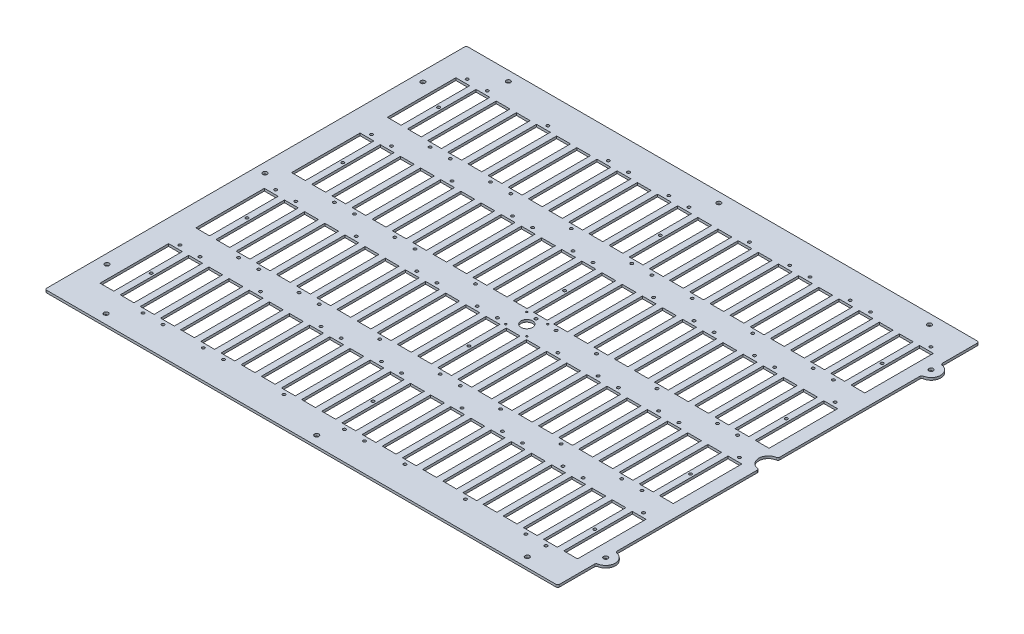
SolidWorks part; units mm, degrees
ref_plane "Front Plane" through (0, 0, 0) normal (0, 0, 1) x (1, 0, 0)
ref_plane "Top Plane" through (0, 0, 0) normal (0, 1, 0) x (1, 0, 0)
ref_plane "Right Plane" through (0, 0, 0) normal (1, 0, 0) x (0, 0, -1)
sketch "Sketch1" plane through (0, 0, 0) normal (0, 1, 0) x (1, 0, 0)
  line L0 (340.2584, 228.6) -> (340.2584, 279.5524)
  line L1 (-340.2584, -279.5524) -> (340.2584, -279.5524)
  line L2 (-340.2584, -279.5524) -> (-340.2584, 279.5524)
  line L3 (-340.2584, 279.5524) -> (340.2584, 279.5524)
  line L4 (340.2584, -279.5524) -> (340.2584, -228.6)
  line L5 (-340.2584, -279.5524) -> (340.2584, 279.5524) construction
  line L6 (-340.2584, 279.5524) -> (340.2584, -279.5524) construction
  line L7 (340.2584, 12.7) -> (340.2584, 203.2)
  line L8 (340.2584, -203.2) -> (340.2584, -12.7)
  arc A0 (340.2584, 203.2) -> (340.2584, 228.6) centre (340.2584, 215.9) ccw
  arc A1 (340.2584, -228.6) -> (340.2584, -203.2) centre (340.2584, -215.9) ccw
  arc A2 (340.2584, 12.7) -> (340.2584, -12.7) centre (340.2584, 0) ccw
  point P0 (0, 0)
  dimension "D3" = 25.4
  dimension "D4" = 63.6524
  dimension "D5" = 215.9
  dimension "D6" = 215.9
  dimension "D1" = 559.1048
  dimension "D2" = 680.5168
extrude "Boss-Extrude1" add sketch "Sketch1" along normal blind 3.175
sketch "Sketch17" plane through (0, 3.175, 0) normal (0, 1, 0) x (1, 0, 0)
  line L0 (340.2584, 279.5524) -> (-340.2584, 279.5524) construction
  line L1 (-314.8584, 254.1524) -> (327.5584, 254.1524) construction
  line L2 (-314.8584, 254.1524) -> (-314.8584, -254.1524) construction
  line L3 (-314.8584, -254.1524) -> (327.5584, -254.1524) construction
  line L4 (327.5584, 254.1524) -> (327.5584, -254.1524) construction
  line L5 (-340.2584, 279.5524) -> (-340.2584, -279.5524) construction
  line L6 (-340.2584, -279.5524) -> (340.2584, -279.5524) construction
  line L7 (340.2584, -203.2) -> (340.2584, -12.7) construction
  line L8 (-283.8406, 236.1184) -> (-265.5526, 236.1184)
  line L9 (-310.5912, 236.1184) -> (-292.3032, 236.1184)
  line L10 (-310.5912, 236.1184) -> (-310.5912, 145.1864)
  line L11 (-310.5912, 145.1864) -> (-292.3032, 145.1864)
  line L12 (-292.3032, 236.1184) -> (-292.3032, 145.1864)
  line L13 (-283.8406, 236.1184) -> (-283.8406, 145.1864)
  line L14 (-265.5526, 236.1184) -> (-265.5526, 145.1864)
  line L15 (-283.8406, 145.1864) -> (-265.5526, 145.1864)
  line L16 (-257.09, 236.1184) -> (-238.802, 236.1184)
  line L17 (-257.09, 236.1184) -> (-257.09, 145.1864)
  line L18 (-238.802, 236.1184) -> (-238.802, 145.1864)
  line L19 (-257.09, 145.1864) -> (-238.802, 145.1864)
  line L20 (-230.3393, 236.1184) -> (-212.0513, 236.1184)
  line L21 (-230.3393, 236.1184) -> (-230.3393, 145.1864)
  line L22 (-212.0513, 236.1184) -> (-212.0513, 145.1864)
  line L23 (-230.3393, 145.1864) -> (-212.0513, 145.1864)
  line L24 (-203.5887, 236.1184) -> (-185.3007, 236.1184)
  line L25 (-203.5887, 236.1184) -> (-203.5887, 145.1864)
  line L26 (-185.3007, 236.1184) -> (-185.3007, 145.1864)
  line L27 (-203.5887, 145.1864) -> (-185.3007, 145.1864)
  line L28 (-176.8381, 236.1184) -> (-158.5501, 236.1184)
  line L29 (-176.8381, 236.1184) -> (-176.8381, 145.1864)
  line L30 (-158.5501, 236.1184) -> (-158.5501, 145.1864)
  line L31 (-176.8381, 145.1864) -> (-158.5501, 145.1864)
  line L32 (-150.0875, 236.1184) -> (-131.7995, 236.1184)
  line L33 (-150.0875, 236.1184) -> (-150.0875, 145.1864)
  line L34 (-131.7995, 236.1184) -> (-131.7995, 145.1864)
  line L35 (-150.0875, 145.1864) -> (-131.7995, 145.1864)
  line L36 (-123.3369, 236.1184) -> (-105.0489, 236.1184)
  line L37 (-123.3369, 236.1184) -> (-123.3369, 145.1864)
  line L38 (-105.0489, 236.1184) -> (-105.0489, 145.1864)
  line L39 (-123.3369, 145.1864) -> (-105.0489, 145.1864)
  line L40 (-96.5863, 236.1184) -> (-78.2983, 236.1184)
  line L41 (-96.5863, 236.1184) -> (-96.5863, 145.1864)
  line L42 (-78.2983, 236.1184) -> (-78.2983, 145.1864)
  line L43 (-96.5863, 145.1864) -> (-78.2983, 145.1864)
  line L44 (-69.8356, 236.1184) -> (-51.5476, 236.1184)
  line L45 (-69.8356, 236.1184) -> (-69.8356, 145.1864)
  line L46 (-51.5476, 236.1184) -> (-51.5476, 145.1864)
  line L47 (-69.8356, 145.1864) -> (-51.5476, 145.1864)
  line L48 (-43.085, 236.1184) -> (-24.797, 236.1184)
  line L49 (-43.085, 236.1184) -> (-43.085, 145.1864)
  line L50 (-24.797, 236.1184) -> (-24.797, 145.1864)
  line L51 (-43.085, 145.1864) -> (-24.797, 145.1864)
  line L52 (-16.3344, 236.1184) -> (1.9536, 236.1184)
  line L53 (-16.3344, 236.1184) -> (-16.3344, 145.1864)
  line L54 (1.9536, 236.1184) -> (1.9536, 145.1864)
  line L55 (-16.3344, 145.1864) -> (1.9536, 145.1864)
  line L56 (10.4162, 236.1184) -> (28.7042, 236.1184)
  line L57 (10.4162, 236.1184) -> (10.4162, 145.1864)
  line L58 (28.7042, 236.1184) -> (28.7042, 145.1864)
  line L59 (10.4162, 145.1864) -> (28.7042, 145.1864)
  line L60 (37.1668, 236.1184) -> (55.4548, 236.1184)
  line L61 (37.1668, 236.1184) -> (37.1668, 145.1864)
  line L62 (55.4548, 236.1184) -> (55.4548, 145.1864)
  line L63 (37.1668, 145.1864) -> (55.4548, 145.1864)
  line L64 (63.9174, 236.1184) -> (82.2054, 236.1184)
  line L65 (63.9174, 236.1184) -> (63.9174, 145.1864)
  line L66 (82.2054, 236.1184) -> (82.2054, 145.1864)
  line L67 (63.9174, 145.1864) -> (82.2054, 145.1864)
  line L68 (90.6681, 236.1184) -> (108.9561, 236.1184)
  line L69 (90.6681, 236.1184) -> (90.6681, 145.1864)
  line L70 (108.9561, 236.1184) -> (108.9561, 145.1864)
  line L71 (90.6681, 145.1864) -> (108.9561, 145.1864)
  line L72 (117.4187, 236.1184) -> (135.7067, 236.1184)
  line L73 (117.4187, 236.1184) -> (117.4187, 145.1864)
  line L74 (135.7067, 236.1184) -> (135.7067, 145.1864)
  line L75 (117.4187, 145.1864) -> (135.7067, 145.1864)
  line L76 (144.1693, 236.1184) -> (162.4573, 236.1184)
  line L77 (144.1693, 236.1184) -> (144.1693, 145.1864)
  line L78 (162.4573, 236.1184) -> (162.4573, 145.1864)
  line L79 (144.1693, 145.1864) -> (162.4573, 145.1864)
  line L80 (170.9199, 236.1184) -> (189.2079, 236.1184)
  line L81 (170.9199, 236.1184) -> (170.9199, 145.1864)
  line L82 (189.2079, 236.1184) -> (189.2079, 145.1864)
  line L83 (170.9199, 145.1864) -> (189.2079, 145.1864)
  line L84 (197.6705, 236.1184) -> (215.9585, 236.1184)
  line L85 (197.6705, 236.1184) -> (197.6705, 145.1864)
  line L86 (215.9585, 236.1184) -> (215.9585, 145.1864)
  line L87 (197.6705, 145.1864) -> (215.9585, 145.1864)
  line L88 (224.4211, 236.1184) -> (242.7091, 236.1184)
  line L89 (224.4211, 236.1184) -> (224.4211, 145.1864)
  line L90 (242.7091, 236.1184) -> (242.7091, 145.1864)
  line L91 (224.4211, 145.1864) -> (242.7091, 145.1864)
  line L92 (251.1718, 236.1184) -> (269.4598, 236.1184)
  line L93 (251.1718, 236.1184) -> (251.1718, 145.1864)
  line L94 (269.4598, 236.1184) -> (269.4598, 145.1864)
  line L95 (251.1718, 145.1864) -> (269.4598, 145.1864)
  line L96 (277.9224, 236.1184) -> (296.2104, 236.1184)
  line L97 (277.9224, 236.1184) -> (277.9224, 145.1864)
  line L98 (296.2104, 236.1184) -> (296.2104, 145.1864)
  line L99 (277.9224, 145.1864) -> (296.2104, 145.1864)
  line L100 (304.673, 236.1184) -> (322.961, 236.1184)
  line L101 (304.673, 236.1184) -> (304.673, 145.1864)
  line L102 (322.961, 236.1184) -> (322.961, 145.1864)
  line L103 (304.673, 145.1864) -> (322.961, 145.1864)
  line L104 (-283.8406, 109.0422) -> (-265.5526, 109.0422)
  line L105 (-283.8406, 109.0422) -> (-283.8406, 18.1102)
  line L106 (-265.5526, 109.0422) -> (-265.5526, 18.1102)
  line L107 (-283.8406, 18.1102) -> (-265.5526, 18.1102)
  line L108 (-257.09, 109.0422) -> (-238.802, 109.0422)
  line L109 (-257.09, 109.0422) -> (-257.09, 18.1102)
  line L110 (-238.802, 109.0422) -> (-238.802, 18.1102)
  line L111 (-257.09, 18.1102) -> (-238.802, 18.1102)
  line L112 (-230.3393, 109.0422) -> (-212.0513, 109.0422)
  line L113 (-230.3393, 109.0422) -> (-230.3393, 18.1102)
  line L114 (-212.0513, 109.0422) -> (-212.0513, 18.1102)
  line L115 (-230.3393, 18.1102) -> (-212.0513, 18.1102)
  line L116 (-203.5887, 109.0422) -> (-185.3007, 109.0422)
  line L117 (-203.5887, 109.0422) -> (-203.5887, 18.1102)
  line L118 (-185.3007, 109.0422) -> (-185.3007, 18.1102)
  line L119 (-203.5887, 18.1102) -> (-185.3007, 18.1102)
  line L120 (-176.8381, 109.0422) -> (-158.5501, 109.0422)
  line L121 (-176.8381, 109.0422) -> (-176.8381, 18.1102)
  line L122 (-158.5501, 109.0422) -> (-158.5501, 18.1102)
  line L123 (-176.8381, 18.1102) -> (-158.5501, 18.1102)
  line L124 (-150.0875, 109.0422) -> (-131.7995, 109.0422)
  line L125 (-150.0875, 109.0422) -> (-150.0875, 18.1102)
  line L126 (-131.7995, 109.0422) -> (-131.7995, 18.1102)
  line L127 (-150.0875, 18.1102) -> (-131.7995, 18.1102)
  line L128 (-123.3369, 109.0422) -> (-105.0489, 109.0422)
  line L129 (-123.3369, 109.0422) -> (-123.3369, 18.1102)
  line L130 (-105.0489, 109.0422) -> (-105.0489, 18.1102)
  line L131 (-123.3369, 18.1102) -> (-105.0489, 18.1102)
  line L132 (-96.5863, 109.0422) -> (-78.2983, 109.0422)
  line L133 (-96.5863, 109.0422) -> (-96.5863, 18.1102)
  line L134 (-78.2983, 109.0422) -> (-78.2983, 18.1102)
  line L135 (-96.5863, 18.1102) -> (-78.2983, 18.1102)
  line L136 (-69.8356, 109.0422) -> (-51.5476, 109.0422)
  line L137 (-69.8356, 109.0422) -> (-69.8356, 18.1102)
  line L138 (-51.5476, 109.0422) -> (-51.5476, 18.1102)
  line L139 (-69.8356, 18.1102) -> (-51.5476, 18.1102)
  line L140 (-43.085, 109.0422) -> (-24.797, 109.0422)
  line L141 (-43.085, 109.0422) -> (-43.085, 18.1102)
  line L142 (-24.797, 109.0422) -> (-24.797, 18.1102)
  line L143 (-43.085, 18.1102) -> (-24.797, 18.1102)
  line L144 (-16.3344, 109.0422) -> (1.9536, 109.0422)
  line L145 (-16.3344, 109.0422) -> (-16.3344, 18.1102)
  line L146 (1.9536, 109.0422) -> (1.9536, 18.1102)
  line L147 (-16.3344, 18.1102) -> (1.9536, 18.1102)
  line L148 (10.4162, 109.0422) -> (28.7042, 109.0422)
  line L149 (10.4162, 109.0422) -> (10.4162, 18.1102)
  line L150 (28.7042, 109.0422) -> (28.7042, 18.1102)
  line L151 (10.4162, 18.1102) -> (28.7042, 18.1102)
  line L152 (37.1668, 109.0422) -> (55.4548, 109.0422)
  line L153 (37.1668, 109.0422) -> (37.1668, 18.1102)
  line L154 (55.4548, 109.0422) -> (55.4548, 18.1102)
  line L155 (37.1668, 18.1102) -> (55.4548, 18.1102)
  line L156 (63.9174, 109.0422) -> (82.2054, 109.0422)
  line L157 (63.9174, 109.0422) -> (63.9174, 18.1102)
  line L158 (82.2054, 109.0422) -> (82.2054, 18.1102)
  line L159 (63.9174, 18.1102) -> (82.2054, 18.1102)
  line L160 (90.6681, 109.0422) -> (108.9561, 109.0422)
  line L161 (90.6681, 109.0422) -> (90.6681, 18.1102)
  line L162 (108.9561, 109.0422) -> (108.9561, 18.1102)
  line L163 (90.6681, 18.1102) -> (108.9561, 18.1102)
  line L164 (117.4187, 109.0422) -> (135.7067, 109.0422)
  line L165 (117.4187, 109.0422) -> (117.4187, 18.1102)
  line L166 (135.7067, 109.0422) -> (135.7067, 18.1102)
  line L167 (117.4187, 18.1102) -> (135.7067, 18.1102)
  line L168 (144.1693, 109.0422) -> (162.4573, 109.0422)
  line L169 (144.1693, 109.0422) -> (144.1693, 18.1102)
  line L170 (162.4573, 109.0422) -> (162.4573, 18.1102)
  line L171 (144.1693, 18.1102) -> (162.4573, 18.1102)
  line L172 (170.9199, 109.0422) -> (189.2079, 109.0422)
  line L173 (170.9199, 109.0422) -> (170.9199, 18.1102)
  line L174 (189.2079, 109.0422) -> (189.2079, 18.1102)
  line L175 (170.9199, 18.1102) -> (189.2079, 18.1102)
  line L176 (197.6705, 109.0422) -> (215.9585, 109.0422)
  line L177 (197.6705, 109.0422) -> (197.6705, 18.1102)
  line L178 (215.9585, 109.0422) -> (215.9585, 18.1102)
  line L179 (197.6705, 18.1102) -> (215.9585, 18.1102)
  line L180 (224.4211, 109.0422) -> (242.7091, 109.0422)
  line L181 (224.4211, 109.0422) -> (224.4211, 18.1102)
  line L182 (242.7091, 109.0422) -> (242.7091, 18.1102)
  line L183 (224.4211, 18.1102) -> (242.7091, 18.1102)
  line L184 (251.1718, 109.0422) -> (269.4598, 109.0422)
  line L185 (251.1718, 109.0422) -> (251.1718, 18.1102)
  line L186 (269.4598, 109.0422) -> (269.4598, 18.1102)
  line L187 (251.1718, 18.1102) -> (269.4598, 18.1102)
  line L188 (277.9224, 109.0422) -> (296.2104, 109.0422)
  line L189 (277.9224, 109.0422) -> (277.9224, 18.1102)
  line L190 (296.2104, 109.0422) -> (296.2104, 18.1102)
  line L191 (277.9224, 18.1102) -> (296.2104, 18.1102)
  line L192 (304.673, 109.0422) -> (322.961, 109.0422)
  line L193 (304.673, 109.0422) -> (304.673, 18.1102)
  line L194 (322.961, 109.0422) -> (322.961, 18.1102)
  line L195 (304.673, 18.1102) -> (322.961, 18.1102)
  line L196 (-283.8406, -18.034) -> (-265.5526, -18.034)
  line L197 (-283.8406, -18.034) -> (-283.8406, -108.966)
  line L198 (-265.5526, -18.034) -> (-265.5526, -108.966)
  line L199 (-283.8406, -108.966) -> (-265.5526, -108.966)
  line L200 (-257.09, -18.034) -> (-238.802, -18.034)
  line L201 (-257.09, -18.034) -> (-257.09, -108.966)
  line L202 (-238.802, -18.034) -> (-238.802, -108.966)
  line L203 (-257.09, -108.966) -> (-238.802, -108.966)
  line L204 (-230.3393, -18.034) -> (-212.0513, -18.034)
  line L205 (-230.3393, -18.034) -> (-230.3393, -108.966)
  line L206 (-212.0513, -18.034) -> (-212.0513, -108.966)
  line L207 (-230.3393, -108.966) -> (-212.0513, -108.966)
  line L208 (-203.5887, -18.034) -> (-185.3007, -18.034)
  line L209 (-203.5887, -18.034) -> (-203.5887, -108.966)
  line L210 (-185.3007, -18.034) -> (-185.3007, -108.966)
  line L211 (-203.5887, -108.966) -> (-185.3007, -108.966)
  line L212 (-176.8381, -18.034) -> (-158.5501, -18.034)
  line L213 (-176.8381, -18.034) -> (-176.8381, -108.966)
  line L214 (-158.5501, -18.034) -> (-158.5501, -108.966)
  line L215 (-176.8381, -108.966) -> (-158.5501, -108.966)
  line L216 (-150.0875, -18.034) -> (-131.7995, -18.034)
  line L217 (-150.0875, -18.034) -> (-150.0875, -108.966)
  line L218 (-131.7995, -18.034) -> (-131.7995, -108.966)
  line L219 (-150.0875, -108.966) -> (-131.7995, -108.966)
  line L220 (-123.3369, -18.034) -> (-105.0489, -18.034)
  line L221 (-123.3369, -18.034) -> (-123.3369, -108.966)
  line L222 (-105.0489, -18.034) -> (-105.0489, -108.966)
  line L223 (-123.3369, -108.966) -> (-105.0489, -108.966)
  line L224 (-96.5863, -18.034) -> (-78.2983, -18.034)
  line L225 (-96.5863, -18.034) -> (-96.5863, -108.966)
  line L226 (-78.2983, -18.034) -> (-78.2983, -108.966)
  line L227 (-96.5863, -108.966) -> (-78.2983, -108.966)
  line L228 (-69.8356, -18.034) -> (-51.5476, -18.034)
  line L229 (-69.8356, -18.034) -> (-69.8356, -108.966)
  line L230 (-51.5476, -18.034) -> (-51.5476, -108.966)
  line L231 (-69.8356, -108.966) -> (-51.5476, -108.966)
  line L232 (-43.085, -18.034) -> (-24.797, -18.034)
  line L233 (-43.085, -18.034) -> (-43.085, -108.966)
  line L234 (-24.797, -18.034) -> (-24.797, -108.966)
  line L235 (-43.085, -108.966) -> (-24.797, -108.966)
  line L236 (-16.3344, -18.034) -> (1.9536, -18.034)
  line L237 (-16.3344, -18.034) -> (-16.3344, -108.966)
  line L238 (1.9536, -18.034) -> (1.9536, -108.966)
  line L239 (-16.3344, -108.966) -> (1.9536, -108.966)
  line L240 (10.4162, -18.034) -> (28.7042, -18.034)
  line L241 (10.4162, -18.034) -> (10.4162, -108.966)
  line L242 (28.7042, -18.034) -> (28.7042, -108.966)
  line L243 (10.4162, -108.966) -> (28.7042, -108.966)
  line L244 (37.1668, -18.034) -> (55.4548, -18.034)
  line L245 (37.1668, -18.034) -> (37.1668, -108.966)
  line L246 (55.4548, -18.034) -> (55.4548, -108.966)
  line L247 (37.1668, -108.966) -> (55.4548, -108.966)
  line L248 (63.9174, -18.034) -> (82.2054, -18.034)
  line L249 (63.9174, -18.034) -> (63.9174, -108.966)
  line L250 (82.2054, -18.034) -> (82.2054, -108.966)
  line L251 (63.9174, -108.966) -> (82.2054, -108.966)
  line L252 (90.6681, -18.034) -> (108.9561, -18.034)
  line L253 (90.6681, -18.034) -> (90.6681, -108.966)
  line L254 (108.9561, -18.034) -> (108.9561, -108.966)
  line L255 (90.6681, -108.966) -> (108.9561, -108.966)
  line L256 (117.4187, -18.034) -> (135.7067, -18.034)
  line L257 (117.4187, -18.034) -> (117.4187, -108.966)
  line L258 (135.7067, -18.034) -> (135.7067, -108.966)
  line L259 (117.4187, -108.966) -> (135.7067, -108.966)
  line L260 (144.1693, -18.034) -> (162.4573, -18.034)
  line L261 (144.1693, -18.034) -> (144.1693, -108.966)
  line L262 (162.4573, -18.034) -> (162.4573, -108.966)
  line L263 (144.1693, -108.966) -> (162.4573, -108.966)
  line L264 (170.9199, -18.034) -> (189.2079, -18.034)
  line L265 (170.9199, -18.034) -> (170.9199, -108.966)
  line L266 (189.2079, -18.034) -> (189.2079, -108.966)
  line L267 (170.9199, -108.966) -> (189.2079, -108.966)
  line L268 (197.6705, -18.034) -> (215.9585, -18.034)
  line L269 (197.6705, -18.034) -> (197.6705, -108.966)
  line L270 (215.9585, -18.034) -> (215.9585, -108.966)
  line L271 (197.6705, -108.966) -> (215.9585, -108.966)
  line L272 (224.4211, -18.034) -> (242.7091, -18.034)
  line L273 (224.4211, -18.034) -> (224.4211, -108.966)
  line L274 (242.7091, -18.034) -> (242.7091, -108.966)
  line L275 (224.4211, -108.966) -> (242.7091, -108.966)
  line L276 (251.1718, -18.034) -> (269.4598, -18.034)
  line L277 (251.1718, -18.034) -> (251.1718, -108.966)
  line L278 (269.4598, -18.034) -> (269.4598, -108.966)
  line L279 (251.1718, -108.966) -> (269.4598, -108.966)
  line L280 (277.9224, -18.034) -> (296.2104, -18.034)
  line L281 (277.9224, -18.034) -> (277.9224, -108.966)
  line L282 (296.2104, -18.034) -> (296.2104, -108.966)
  line L283 (277.9224, -108.966) -> (296.2104, -108.966)
  line L284 (304.673, -18.034) -> (322.961, -18.034)
  line L285 (304.673, -18.034) -> (304.673, -108.966)
  line L286 (322.961, -18.034) -> (322.961, -108.966)
  line L287 (304.673, -108.966) -> (322.961, -108.966)
  line L288 (-283.8406, -145.1102) -> (-265.5526, -145.1102)
  line L289 (-283.8406, -145.1102) -> (-283.8406, -236.0422)
  line L290 (-265.5526, -145.1102) -> (-265.5526, -236.0422)
  line L291 (-283.8406, -236.0422) -> (-265.5526, -236.0422)
  line L292 (-257.09, -145.1102) -> (-238.802, -145.1102)
  line L293 (-257.09, -145.1102) -> (-257.09, -236.0422)
  line L294 (-238.802, -145.1102) -> (-238.802, -236.0422)
  line L295 (-257.09, -236.0422) -> (-238.802, -236.0422)
  line L296 (-230.3393, -145.1102) -> (-212.0513, -145.1102)
  line L297 (-230.3393, -145.1102) -> (-230.3393, -236.0422)
  line L298 (-212.0513, -145.1102) -> (-212.0513, -236.0422)
  line L299 (-230.3393, -236.0422) -> (-212.0513, -236.0422)
  line L300 (-203.5887, -145.1102) -> (-185.3007, -145.1102)
  line L301 (-203.5887, -145.1102) -> (-203.5887, -236.0422)
  line L302 (-185.3007, -145.1102) -> (-185.3007, -236.0422)
  line L303 (-203.5887, -236.0422) -> (-185.3007, -236.0422)
  line L304 (-176.8381, -145.1102) -> (-158.5501, -145.1102)
  line L305 (-176.8381, -145.1102) -> (-176.8381, -236.0422)
  line L306 (-158.5501, -145.1102) -> (-158.5501, -236.0422)
  line L307 (-176.8381, -236.0422) -> (-158.5501, -236.0422)
  line L308 (-150.0875, -145.1102) -> (-131.7995, -145.1102)
  line L309 (-150.0875, -145.1102) -> (-150.0875, -236.0422)
  line L310 (-131.7995, -145.1102) -> (-131.7995, -236.0422)
  line L311 (-150.0875, -236.0422) -> (-131.7995, -236.0422)
  line L312 (-123.3369, -145.1102) -> (-105.0489, -145.1102)
  line L313 (-123.3369, -145.1102) -> (-123.3369, -236.0422)
  line L314 (-105.0489, -145.1102) -> (-105.0489, -236.0422)
  line L315 (-123.3369, -236.0422) -> (-105.0489, -236.0422)
  line L316 (-96.5863, -145.1102) -> (-78.2983, -145.1102)
  line L317 (-96.5863, -145.1102) -> (-96.5863, -236.0422)
  line L318 (-78.2983, -145.1102) -> (-78.2983, -236.0422)
  line L319 (-96.5863, -236.0422) -> (-78.2983, -236.0422)
  line L320 (-69.8356, -145.1102) -> (-51.5476, -145.1102)
  line L321 (-69.8356, -145.1102) -> (-69.8356, -236.0422)
  line L322 (-51.5476, -145.1102) -> (-51.5476, -236.0422)
  line L323 (-69.8356, -236.0422) -> (-51.5476, -236.0422)
  line L324 (-43.085, -145.1102) -> (-24.797, -145.1102)
  line L325 (-43.085, -145.1102) -> (-43.085, -236.0422)
  line L326 (-24.797, -145.1102) -> (-24.797, -236.0422)
  line L327 (-43.085, -236.0422) -> (-24.797, -236.0422)
  line L328 (-16.3344, -145.1102) -> (1.9536, -145.1102)
  line L329 (-16.3344, -145.1102) -> (-16.3344, -236.0422)
  line L330 (1.9536, -145.1102) -> (1.9536, -236.0422)
  line L331 (-16.3344, -236.0422) -> (1.9536, -236.0422)
  line L332 (10.4162, -145.1102) -> (28.7042, -145.1102)
  line L333 (10.4162, -145.1102) -> (10.4162, -236.0422)
  line L334 (28.7042, -145.1102) -> (28.7042, -236.0422)
  line L335 (10.4162, -236.0422) -> (28.7042, -236.0422)
  line L336 (37.1668, -145.1102) -> (55.4548, -145.1102)
  line L337 (37.1668, -145.1102) -> (37.1668, -236.0422)
  line L338 (55.4548, -145.1102) -> (55.4548, -236.0422)
  line L339 (37.1668, -236.0422) -> (55.4548, -236.0422)
  line L340 (63.9174, -145.1102) -> (82.2054, -145.1102)
  line L341 (63.9174, -145.1102) -> (63.9174, -236.0422)
  line L342 (82.2054, -145.1102) -> (82.2054, -236.0422)
  line L343 (63.9174, -236.0422) -> (82.2054, -236.0422)
  line L344 (90.6681, -145.1102) -> (108.9561, -145.1102)
  line L345 (90.6681, -145.1102) -> (90.6681, -236.0422)
  line L346 (108.9561, -145.1102) -> (108.9561, -236.0422)
  line L347 (90.6681, -236.0422) -> (108.9561, -236.0422)
  line L348 (117.4187, -145.1102) -> (135.7067, -145.1102)
  line L349 (117.4187, -145.1102) -> (117.4187, -236.0422)
  line L350 (135.7067, -145.1102) -> (135.7067, -236.0422)
  line L351 (117.4187, -236.0422) -> (135.7067, -236.0422)
  line L352 (144.1693, -145.1102) -> (162.4573, -145.1102)
  line L353 (144.1693, -145.1102) -> (144.1693, -236.0422)
  line L354 (162.4573, -145.1102) -> (162.4573, -236.0422)
  line L355 (144.1693, -236.0422) -> (162.4573, -236.0422)
  line L356 (170.9199, -145.1102) -> (189.2079, -145.1102)
  line L357 (170.9199, -145.1102) -> (170.9199, -236.0422)
  line L358 (189.2079, -145.1102) -> (189.2079, -236.0422)
  line L359 (170.9199, -236.0422) -> (189.2079, -236.0422)
  line L360 (197.6705, -145.1102) -> (215.9585, -145.1102)
  line L361 (197.6705, -145.1102) -> (197.6705, -236.0422)
  line L362 (215.9585, -145.1102) -> (215.9585, -236.0422)
  line L363 (197.6705, -236.0422) -> (215.9585, -236.0422)
  line L364 (224.4211, -145.1102) -> (242.7091, -145.1102)
  line L365 (224.4211, -145.1102) -> (224.4211, -236.0422)
  line L366 (242.7091, -145.1102) -> (242.7091, -236.0422)
  line L367 (224.4211, -236.0422) -> (242.7091, -236.0422)
  line L368 (251.1718, -145.1102) -> (269.4598, -145.1102)
  line L369 (251.1718, -145.1102) -> (251.1718, -236.0422)
  line L370 (269.4598, -145.1102) -> (269.4598, -236.0422)
  line L371 (251.1718, -236.0422) -> (269.4598, -236.0422)
  line L372 (277.9224, -145.1102) -> (296.2104, -145.1102)
  line L373 (277.9224, -145.1102) -> (277.9224, -236.0422)
  line L374 (296.2104, -145.1102) -> (296.2104, -236.0422)
  line L375 (277.9224, -236.0422) -> (296.2104, -236.0422)
  line L376 (304.673, -145.1102) -> (322.961, -145.1102)
  line L377 (304.673, -145.1102) -> (304.673, -236.0422)
  line L378 (322.961, -145.1102) -> (322.961, -236.0422)
  line L379 (304.673, -236.0422) -> (322.961, -236.0422)
  line L380 (-310.5912, 109.0422) -> (-292.3032, 109.0422)
  line L381 (-310.5912, 109.0422) -> (-310.5912, 18.1102)
  line L382 (-292.3032, 109.0422) -> (-292.3032, 18.1102)
  line L383 (-310.5912, 18.1102) -> (-292.3032, 18.1102)
  line L384 (-310.5912, -18.034) -> (-292.3032, -18.034)
  line L385 (-310.5912, -18.034) -> (-310.5912, -108.966)
  line L386 (-292.3032, -18.034) -> (-292.3032, -108.966)
  line L387 (-310.5912, -108.966) -> (-292.3032, -108.966)
  line L388 (-310.5912, -145.1102) -> (-292.3032, -145.1102)
  line L389 (-310.5912, -145.1102) -> (-310.5912, -236.0422)
  line L390 (-292.3032, -145.1102) -> (-292.3032, -236.0422)
  line L391 (-310.5912, -236.0422) -> (-292.3032, -236.0422)
  line L392 (340.2584, -279.5524) -> (340.2584, -228.6) construction
  dimension "D1" = 25.4
  dimension "D2" = 25.4
  dimension "D3" = 25.4
  dimension "D4" = 12.7
  dimension "D5" = 18.288
  dimension "D6" = 90.932
  dimension "D7" = 4.2672
  dimension "D8" = 18.034
  dimension "D9" = 508.3048
  dimension "D10" = 642.4168
  dimension "D11" = 24
  dimension "D13" = 17.2974
  dimension "D14" = 43.5102
  dimension "D12" = 4
extrude "Cut-Extrude5" cut sketch "Sketch17" against normal through all
hole_wizard "#25 (0.1495) Diameter Hole1" positions "Sketch18" profile "Sketch19" hole size "#25" standard "ANSI Inch" end condition through all
sketch "Sketch18" plane through (0, 3.175, 0) normal (0, 1, 0) x (1, 0, 0)
  line L10 (-340.2584, 241.9604) -> (340.2584, 241.9604) construction
  line L11 (-340.2584, 279.5524) -> (-340.2584, -279.5524) construction
  line L12 (340.2584, 228.6) -> (340.2584, 279.5524) construction
  line L15 (-292.3032, 236.1184) -> (-310.5912, 236.1184) construction
  line L16 (-340.2584, 139.3444) -> (340.2584, 139.3444) construction
  line L17 (340.2584, 12.7) -> (340.2584, 203.2) construction
  line L19 (-310.5912, 145.1864) -> (-292.3032, 145.1864) construction
  line L23 (-301.4472, 139.3444) -> (-301.4472, 241.9604) construction
  line L24 (-274.6966, 139.3444) -> (-274.6966, 241.9604) construction
  line L25 (-247.946, 139.3444) -> (-247.946, 241.9604) construction
  line L26 (-221.1953, 139.3444) -> (-221.1953, 241.9604) construction
  line L27 (-194.4447, 139.3444) -> (-194.4447, 241.9604) construction
  line L28 (-167.6941, 139.3444) -> (-167.6941, 241.9604) construction
  line L29 (-140.9435, 139.3444) -> (-140.9435, 241.9604) construction
  line L30 (-114.1929, 139.3444) -> (-114.1929, 241.9604) construction
  line L31 (-87.4423, 139.3444) -> (-87.4423, 241.9604) construction
  line L32 (-60.6916, 139.3444) -> (-60.6916, 241.9604) construction
  line L33 (-33.941, 139.3444) -> (-33.941, 241.9604) construction
  line L34 (-7.1904, 139.3444) -> (-7.1904, 241.9604) construction
  line L35 (19.5602, 139.3444) -> (19.5602, 241.9604) construction
  line L36 (46.3108, 139.3444) -> (46.3108, 241.9604) construction
  line L37 (73.0614, 139.3444) -> (73.0614, 241.9604) construction
  line L38 (99.8121, 139.3444) -> (99.8121, 241.9604) construction
  line L39 (126.5627, 139.3444) -> (126.5627, 241.9604) construction
  line L40 (153.3133, 139.3444) -> (153.3133, 241.9604) construction
  line L41 (180.0639, 139.3444) -> (180.0639, 241.9604) construction
  line L42 (206.8145, 139.3444) -> (206.8145, 241.9604) construction
  line L43 (233.5651, 139.3444) -> (233.5651, 241.9604) construction
  line L44 (260.3158, 139.3444) -> (260.3158, 241.9604) construction
  line L45 (287.0664, 139.3444) -> (287.0664, 241.9604) construction
  line L46 (313.817, 139.3444) -> (313.817, 241.9604) construction
  point P259 (-301.4472, 241.9604)
  point P269 (-274.6966, 241.9604)
  point P270 (-247.946, 139.3444)
  point P272 (-221.1953, 139.3444)
  point P275 (-194.4447, 241.9604)
  point P276 (-167.6941, 139.3444)
  point P278 (-140.9435, 139.3444)
  point P281 (-114.1929, 241.9604)
  point P283 (-87.4423, 241.9604)
  point P284 (-60.6916, 139.3444)
  point P287 (-33.941, 241.9604)
  point P289 (-7.1904, 241.9604)
  point P290 (19.5602, 139.3444)
  point P292 (46.3108, 139.3444)
  point P295 (73.0614, 241.9604)
  point P296 (99.8121, 139.3444)
  point P299 (126.5627, 241.9604)
  point P301 (153.3133, 241.9604)
  point P302 (180.0639, 139.3444)
  point P305 (206.8145, 241.9604)
  point P307 (233.5651, 241.9604)
  point P308 (260.3158, 139.3444)
  point P310 (287.0664, 139.3444)
  point P313 (313.817, 241.9604)
  point P365 (-301.4472, 114.8842)
  point P366 (-274.6966, 114.8842)
  point P367 (-247.946, 12.2682)
  point P368 (-221.1953, 12.2682)
  point P369 (-194.4447, 114.8842)
  point P370 (-167.6941, 12.2682)
  point P371 (-140.9435, 12.2682)
  point P372 (-114.1929, 114.8842)
  point P373 (-87.4423, 114.8842)
  point P374 (-60.6916, 12.2682)
  point P375 (-33.941, 114.8842)
  point P376 (-7.1904, 114.8842)
  point P377 (19.5602, 12.2682)
  point P378 (46.3108, 12.2682)
  point P379 (73.0614, 114.8842)
  point P380 (99.8121, 12.2682)
  point P381 (126.5627, 114.8842)
  point P382 (153.3133, 114.8842)
  point P383 (180.0639, 12.2682)
  point P384 (206.8145, 114.8842)
  point P385 (233.5651, 114.8842)
  point P386 (260.3158, 12.2682)
  point P387 (287.0664, 12.2682)
  point P388 (313.817, 114.8842)
  point P389 (-301.4472, -12.192)
  point P390 (-274.6966, -12.192)
  point P391 (-247.946, -114.808)
  point P392 (-221.1953, -114.808)
  point P393 (-194.4447, -12.192)
  point P394 (-167.6941, -114.808)
  point P395 (-140.9435, -114.808)
  point P396 (-114.1929, -12.192)
  point P397 (-87.4423, -12.192)
  point P398 (-60.6916, -114.808)
  point P399 (-33.941, -12.192)
  point P400 (-7.1904, -12.192)
  point P401 (19.5602, -114.808)
  point P402 (46.3108, -114.808)
  point P403 (73.0614, -12.192)
  point P404 (99.8121, -114.808)
  point P405 (126.5627, -12.192)
  point P406 (153.3133, -12.192)
  point P407 (180.0639, -114.808)
  point P408 (206.8145, -12.192)
  point P409 (233.5651, -12.192)
  point P410 (260.3158, -114.808)
  point P411 (287.0664, -114.808)
  point P412 (313.817, -12.192)
  point P413 (-301.4472, -139.2682)
  point P414 (-274.6966, -139.2682)
  point P415 (-247.946, -241.8842)
  point P416 (-221.1953, -241.8842)
  point P417 (-194.4447, -139.2682)
  point P418 (-167.6941, -241.8842)
  point P419 (-140.9435, -241.8842)
  point P420 (-114.1929, -139.2682)
  point P421 (-87.4423, -139.2682)
  point P422 (-60.6916, -241.8842)
  point P423 (-33.941, -139.2682)
  point P424 (-7.1904, -139.2682)
  point P425 (19.5602, -241.8842)
  point P426 (46.3108, -241.8842)
  point P427 (73.0614, -139.2682)
  point P428 (99.8121, -241.8842)
  point P429 (126.5627, -139.2682)
  point P430 (153.3133, -139.2682)
  point P431 (180.0639, -241.8842)
  point P432 (206.8145, -139.2682)
  point P433 (233.5651, -139.2682)
  point P434 (260.3158, -241.8842)
  point P435 (287.0664, -241.8842)
  point P436 (313.817, -139.2682)
  dimension "D1" = 5.842
  dimension "D2" = 5.842
sketch "Sketch19" plane through (313.817, 3.175, 139.2682) normal (1, 0, 0) x (0, 0, 1)
  line L0 (0, 0) -> (0, 3.175)
  line L1 (0, 3.175) -> (1.8986, 3.175)
  line L2 (1.8986, 3.175) -> (1.8986, 0)
  line L5 (1.8986, 0) -> (0, 0)
  line L11 (0, -6.35) -> (0, 107.95) construction
  dimension "Thru Hole Dia." = 3.7973
  dimension "Thru Hole Depth" = 3.175
fillet "Fillet1" radius 2.54 10 edges at (-340.2584, 1.5875, -279.5524) (-340.2584, 1.5875, 279.5524) (340.2584, 1.5875, 279.5524) (340.2584, 1.5875, 228.6) (340.2584, 1.5875, 203.2) (340.2584, 1.5875, 12.7) (340.2584, 1.5875, -12.7) (340.2584, 1.5875, -203.2) (340.2584, 1.5875, -279.5524) (340.2584, 1.5875, -228.6)
hole_wizard "#6 Clearance Hole1" positions "Sketch8" profile "Sketch9" hole size "#6" standard "ANSI Inch" end condition through all
sketch "Sketch8" plane through (0, 3.175, 0) normal (0, 1, 0) x (1, 0, 0)
  line L13 (-292.3032, 236.1184) -> (-283.8406, 145.1864) construction
  line L15 (1.9536, 236.1184) -> (10.4162, 145.1864) construction
  line L17 (296.2104, 236.1184) -> (304.673, 145.1864) construction
  line L18 (-292.3032, 109.0422) -> (-283.8406, 18.1102) construction
  line L19 (1.9536, 109.0422) -> (10.4162, 18.1102) construction
  line L20 (296.2104, 109.0422) -> (304.673, 18.1102) construction
  line L21 (-292.3032, -18.034) -> (-283.8406, -108.966) construction
  line L22 (1.9536, -18.034) -> (10.4162, -108.966) construction
  line L23 (296.2104, -18.034) -> (304.673, -108.966) construction
  line L24 (-292.3032, -145.1102) -> (-283.8406, -236.0422) construction
  line L25 (1.9536, -145.1102) -> (10.4162, -236.0422) construction
  line L26 (296.2104, -145.1102) -> (304.673, -236.0422) construction
  point P129 (-288.0719, 190.6524)
  point P131 (6.1849, 190.6524)
  point P133 (300.4417, 190.6524)
  point P146 (-288.0719, 63.5762)
  point P147 (6.1849, 63.5762)
  point P148 (300.4417, 63.5762)
  point P155 (-288.0719, -63.5)
  point P156 (6.1849, -63.5)
  point P157 (300.4417, -63.5)
  point P164 (-288.0719, -190.5762)
  point P165 (6.1849, -190.5762)
  point P166 (300.4417, -190.5762)
  dimension "D1" = 4
sketch "Sketch9" plane through (300.4417, 3.175, 190.5762) normal (1, 0, 0) x (0, 0, 1)
  line L0 (0, 0) -> (0, 3.175)
  line L1 (0, 3.175) -> (1.8986, 3.175)
  line L2 (1.8986, 3.175) -> (1.8986, 0)
  line L5 (1.8986, 0) -> (0, 0)
  line L11 (0, -6.35) -> (0, 107.95) construction
  dimension "Thru Hole Dia." = 3.7973
  dimension "Thru Hole Depth" = 3.175
hole_wizard "#2 Clearance Hole1" positions "Sketch13" profile "Sketch14" hole size "#2" standard "ANSI Inch" end condition through all
sketch "Sketch13" plane through (0, 3.175, 0) normal (0, 1, 0) x (1, 0, 0)
  line L9 (322.961, -108.966) -> (322.961, -18.034) construction
  line L10 (322.961, -18.034) -> (304.673, -18.034) construction
  line L18 (10.4162, 18.1102) -> (28.7042, -18.034) construction
  line L21 (5.6261, -13.9319) -> (33.5661, -13.9319) construction
  line L22 (5.6261, -13.9319) -> (5.6261, 14.0081) construction
  line L23 (5.6261, 14.0081) -> (33.5661, 14.0081) construction
  line L24 (33.5661, -13.9319) -> (33.5661, 14.0081) construction
  line L25 (5.6261, -13.9319) -> (33.5661, 14.0081) construction
  line L26 (5.6261, 14.0081) -> (33.5661, -13.9319) construction
  line L27 (10.4162, 18.1102) -> (28.7042, 18.1102) construction
  point P129 (5.6261, 14.0081)
  point P132 (5.6261, -13.9319)
  point P135 (33.5661, -13.9319)
  point P138 (33.5661, 14.0081)
  dimension "D1" = 27.94
  dimension "D2" = 27.94
  dimension "D3" = 4.1021
sketch "Sketch14" plane through (33.5661, 3.175, -14.0081) normal (1, 0, 0) x (0, 0, 1)
  line L0 (0, 0) -> (0, 3.175)
  line L1 (0, 3.175) -> (1.2192, 3.175)
  line L2 (1.2192, 3.175) -> (1.2192, 0)
  line L5 (1.2192, 0) -> (0, 0)
  line L11 (0, -6.35) -> (0, 107.95) construction
  dimension "Thru Hole Dia." = 2.4384
  dimension "Thru Hole Depth" = 3.175
sketch "Sketch20" plane through (0, 3.175, 0) normal (0, 1, 0) x (1, 0, 0)
  line L0 (5.6261, 14.0081) -> (33.5661, -13.9319) construction
  circle A0 centre (19.5961, 0.0381) radius 7.62
  dimension "D1" = 15.24
extrude "Cut-Extrude6" cut sketch "Sketch20" against normal through all
hole_wizard "#1 (0.228) Diameter Hole1" positions "Sketch21" profile "Sketch22" hole size "#1" standard "ANSI Inch" end condition through all
sketch "Sketch21" plane through (0, 3.175, 0) normal (0, 1, 0) x (1, 0, 0)
  point P0 (287.274, 266.7)
  point P3 (340.2584, -215.9)
  point P6 (340.2584, 0)
  point P9 (340.2584, 215.9)
  point P12 (287.274, -267.0048)
  point P15 (7.874, -267.0048)
  point P18 (-271.526, -267.0048)
  point P21 (-327.5584, -209.7024)
  point P24 (-327.5584, -0.1524)
  point P27 (-327.5584, 209.3976)
  point P30 (-271.526, 266.7)
  point P33 (7.874, 266.7)
sketch "Sketch22" plane through (287.274, 3.175, -266.7) normal (1, 0, 0) x (0, 0, 1)
  line L0 (0, 0) -> (0, 3.175)
  line L1 (0, 3.175) -> (2.8956, 3.175)
  line L2 (2.8956, 3.175) -> (2.8956, 0)
  line L5 (2.8956, 0) -> (0, 0)
  line L11 (0, -6.35) -> (0, 107.95) construction
  dimension "Thru Hole Dia." = 5.7912
  dimension "Thru Hole Depth" = 3.175
